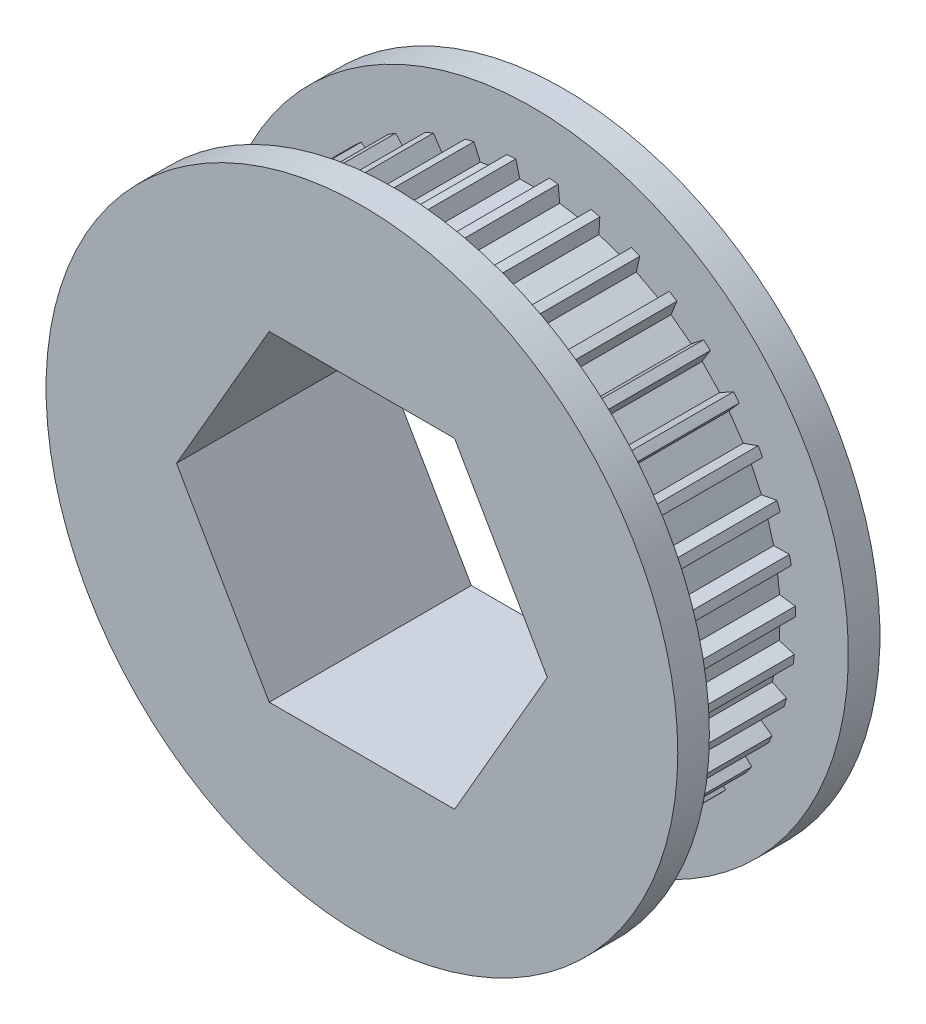
SolidWorks part; units mm, degrees
ref_plane "Front Plane" through (0, 0, 0) normal (0, 0, 1) x (1, 0, 0)
ref_plane "Top Plane" through (0, 0, 0) normal (0, 1, 0) x (1, 0, 0)
ref_plane "Right Plane" through (0, 0, 0) normal (1, 0, 0) x (0, 0, -1)
sketch "Sketch1" plane through (0, 0, 0) normal (0, 0, 1) x (1, 0, 0)
  circle A0 centre (0, 0) radius 12.5
  dimension "D1" = 25
extrude "Boss-Extrude1" add sketch "Sketch1" along normal mid plane 6.6
sketch "Sketch3" plane through (0, 0, 3.3) normal (0, 0, 1) x (1, 0, 0)
  circle A0 centre (0, 0) radius 15
  dimension "D1" = 30
sketch "Sketch2" plane through (0, 0, -3.3) normal (0, 0, -1) x (-1, 0, 0)
  circle A0 centre (0, 0) radius 15
  dimension "D1" = 30
sketch "Sketch4" plane through (0, 0, 3.3) normal (0, 0, 1) x (1, 0, 0)
  line L0 (-0.6, 11.75) -> (0.6, 11.75)
  line L1 (0.6, 11.75) -> (0.8, 12.5)
  line L2 (0.8, 12.5) -> (-0.8, 12.5)
  line L3 (-0.8, 12.5) -> (-0.6, 11.75)
  circle A0 centre (0, 0) radius 12.5 construction
  point P10 (0, 11.75)
  dimension "D1" = 1.2
  dimension "D2" = 1.6
  dimension "D3" = 0.75
extrude "Cut-Extrude1" cut sketch "Sketch4" against normal up to surface (6.6 mm away) and the other way through all up to face at (12.5, 0, -3.3)
pattern_circular "CirPattern2" count 39 over 360 about axis through (0, 0, 3.3) along (0, 0, 1) of "Cut-Extrude1"
extrude "Boss-Extrude3" add sketch "Sketch2" along normal blind 1.5
extrude "Boss-Extrude4" add sketch "Sketch3" along normal blind 1.5 contours A0
sketch "Sketch5" plane through (0, 0, 4.8) normal (0, 0, 1) x (1, 0, 0)
  line L1 (8.8046, 0) -> (4.4023, 7.625)
  line L2 (4.4023, 7.625) -> (-4.4023, 7.625)
  line L3 (-4.4023, 7.625) -> (-8.8046, 0)
  line L4 (-8.8046, 0) -> (-4.4023, -7.625)
  line L5 (-4.4023, -7.625) -> (4.4023, -7.625)
  line L6 (4.4023, -7.625) -> (8.8046, 0)
  circle A0 centre (0, 0) radius 7.625 construction
  point P1 (0, -7.625)
  dimension "D1" = 15.25
extrude "Cut-Extrude2" cut sketch "Sketch5" against normal through all both and the other way through all
